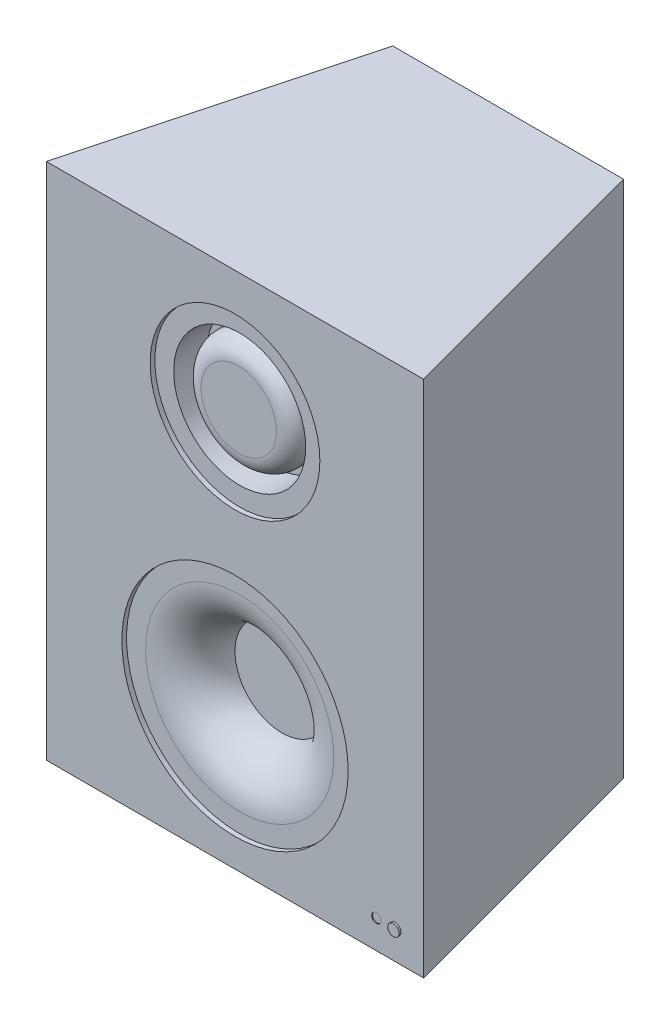
SolidWorks part; units mm, degrees
material "Cedar"
ref_plane "Front Plane" through (0, 0, 0) normal (0, 0, 1) x (1, 0, 0)
ref_plane "Top Plane" through (0, 0, 0) normal (0, 1, 0) x (1, 0, 0)
ref_plane "Right Plane" through (0, 0, 0) normal (1, 0, 0) x (0, 0, -1)
sketch "Sketch1" plane through (0, 0, 0) normal (0, 1, 0) x (1, 0, 0)
  line L0 (-25.4, 0) -> (25.4, 0)
  line L1 (-25.4, 0) -> (-15.539, 36.8018)
  line L2 (-15.539, 36.8018) -> (15.539, 36.8018)
  line L3 (15.539, 36.8018) -> (25.4, 0)
  point P4 (0, 0)
  dimension "D1" = 75
  dimension "D2" = 75
  dimension "D3" = 50.8
  dimension "D4" = 38.1
extrude "Boss-Extrude1" add sketch "Sketch1" along normal blind 69.85
sketch "Sketch3" plane through (0, 0, 0) normal (0, 0, 1) x (1, 0, 0)
  line L0 (0, 0) -> (0, 69.85) construction
  line L1 (-25.4, 69.85) -> (25.4, 69.85) construction
  circle A0 centre (0, 19.05) radius 15.24
  circle A1 centre (0, 53.34) radius 11.43
  circle A2 centre (0, 19.05) radius 6.35
  circle A3 centre (0, 53.34) radius 8.89
  circle A4 centre (0, 53.34) radius 7.62
  dimension "D3" = 30.48
  dimension "D4" = 12.7
  dimension "D5" = 22.86
  dimension "D6" = 17.78
  dimension "D7" = 15.24
  dimension "D1" = 19.05
  dimension "D2" = 53.34
extrude "Cut-Extrude1" cut sketch "Sketch3" against normal blind 0.635 contours A1 | A3
extrude "Cut-Extrude2" cut sketch "Sketch3<4>" against normal blind 5.08 contours A3 | A4
sketch "Sketch3<4>" plane through (0, 0, 0) normal (0, 0, 1) x (1, 0, 0) same geometry as "Sketch3"
extrude "Cut-Extrude3" cut sketch "Sketch3<5>" against normal blind 0.508 contours A4
sketch "Sketch3<5>" plane through (0, 0, 0) normal (0, 0, 1) x (1, 0, 0) same geometry as "Sketch3"
fillet "Fillet1" radius 2.54 1 edges at (7.62, 53.34, -0.508)
extrude "Cut-Extrude4" cut sketch "Sketch3<6>" against normal blind 0.635 contours A0 | A2
sketch "Sketch3<6>" plane through (0, 0, 0) normal (0, 0, 1) x (1, 0, 0) same geometry as "Sketch3"
extrude "Cut-Extrude5" cut sketch "Sketch3<7>" against normal blind 6.35 contours A2
sketch "Sketch3<7>" plane through (0, 0, 0) normal (0, 0, 1) x (1, 0, 0) same geometry as "Sketch3"
fillet "Fillet5" radius 6.35 1 edges at (6.35, 19.05, -0.635)
sketch "Sketch7" plane through (0, 0, 0) normal (0, 0, 1) x (1, 0, 0)
  line L0 (0, 0) -> (38.1, 0) construction
  line L1 (21.59, 0) -> (21.59, 3.81) construction
  line L2 (19.05, 0) -> (19.05, 3.81) construction
  circle A0 centre (21.59, 3.81) radius 0.7641
  circle A1 centre (19.05, 3.81) radius 0.635
  dimension "D5" = 1.27
  dimension "D1" = 21.59
  dimension "D2" = 19.05
  dimension "D3" = 3.81
  dimension "D4" = 3.81
extrude "Boss-Extrude3" add sketch "Sketch7" along normal blind 0.254 contours A0
extrude "Cut-Extrude6" cut sketch "Sketch7<4>" against normal blind 0.127 contours A1
sketch "Sketch7<4>" plane through (0, 0, 0) normal (0, 0, 1) x (1, 0, 0) same geometry as "Sketch7"
sketch "Sketch8" plane through (0, 0, 0) normal (0, -1, 0) x (1, 0, 0)
  line L0 (0, 0) -> (0, -40.1992) construction
  line L1 (-17.9135, -27.94) -> (17.9135, -27.94) construction
  line L2 (-15.539, -36.8018) -> (-25.4, 0) construction
  line L3 (25.4, 0) -> (15.539, -36.8018) construction
  line L4 (-25.4, 0) -> (25.4, 0) construction
  circle A0 centre (0, -27.94) radius 3.175
  dimension "D2" = 6.35
  dimension "D1" = 27.94
extrude "Cut-Extrude7" cut sketch "Sketch8" against normal blind 2.54
scale "Scale1" bodies to scale 110 scale about centroid uniform scaling yes scale factor 2
